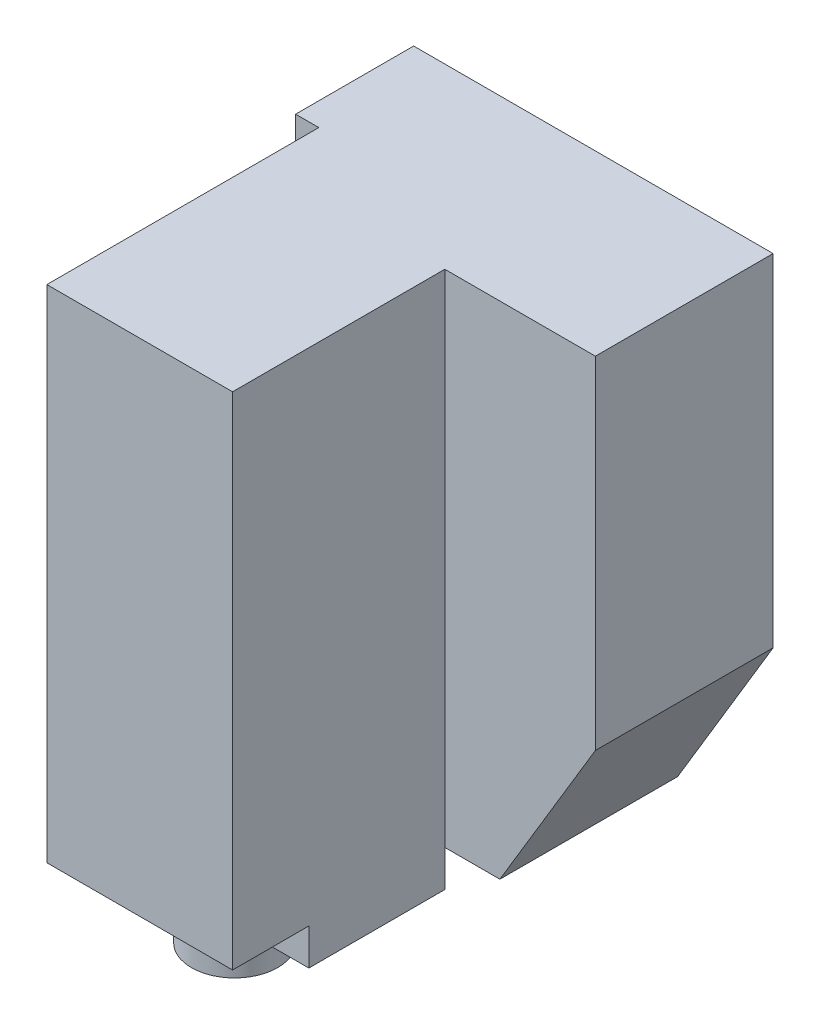
SolidWorks part; units mm, degrees
ref_plane "Front Plane" through (0, 0, 0) normal (0, 0, 1) x (1, 0, 0)
ref_plane "Top Plane" through (0, 0, 0) normal (0, 1, 0) x (1, 0, 0)
ref_plane "Right Plane" through (0, 0, 0) normal (1, 0, 0) x (0, 0, -1)
sketch "Sketch1" plane through (0, 0, 0) normal (0, 0, 1) x (1, 0, 0)
  line L0 (-280, 755) -> (-280, 0)
  line L1 (-280, 0) -> (0, 0)
  line L2 (0, 0) -> (0, 755)
  line L3 (-280, 755) -> (0, 755)
  dimension "D1" = 280
  dimension "D2" = 755
extrude "Boss-Extrude1" add sketch "Sketch1" along normal blind 588
sketch "Sketch4" plane through (0, 0, 0) normal (0, -1, 0) x (1, 0, 0)
  line L1 (-280, 588) -> (0, 588) construction
  line L5 (-280, 588) -> (-280, 0) construction
  circle A0 centre (-160, 425) radius 65
  circle A1 centre (-160, 425) radius 81
  circle A2 centre (-160, 425) radius 37
  dimension "D1" = 130
  dimension "D2" = 16
  dimension "D3" = 82
  dimension "D4" = 39
  dimension "D5" = 74
extrude "Boss-Extrude2" add sketch "Sketch4" along normal blind 20 contours A1
extrude "Boss-Extrude3" add sketch "Sketch4<3>" along normal blind 106 from surface contours A0 starting at face at (-160, -20, 344)
sketch "Sketch4<3>" plane through (0, 0, 0) normal (0, -1, 0) x (1, 0, 0) same geometry as "Sketch4"
extrude "Boss-Extrude4" add sketch "Sketch4<4>" along normal blind 13 from surface contours A2 region at (-160, 0, 425) starting at face at (-160, -126, 360)
sketch "Sketch4<4>" plane through (0, 0, 0) normal (0, -1, 0) x (1, 0, 0) same geometry as "Sketch4"
ref_plane "Plane1" through (0, 0, 268) normal (0, 0, 1) x (1, 0, 0)
sketch "Sketch5" plane through (0, 0, 268) normal (0, 0, -1) x (-1, 0, 0)
  line L0 (0, 0) -> (-83, 0)
  line L1 (-83, 0) -> (-227, 240.1333)
  line L2 (-227, 240.1333) -> (-227, 755)
  line L3 (-227, 755) -> (0, 755)
  line L4 (0, 755) -> (0, 0)
  line L5 (0, 755) -> (280, 755) construction
  dimension "D1" = 83
  dimension "D2" = 227
  dimension "D3" = 280
extrude "Boss-Extrude5" add sketch "Sketch5" along normal up to surface (268 mm away) contours L2 L3 L4 L0 L1 up to face at (-140, 377.5, 0)
ref_plane "Plane2" through (0, 0, 178) normal (0, 0, 1) x (1, 0, 0)
sketch "Sketch6" plane through (0, 0, 178) normal (0, 0, 1) x (1, 0, 0)
  line L0 (-315, -70) -> (-315, 755)
  line L1 (-315, 755) -> (-280, 755)
  line L2 (-280, 755) -> (-280, 0) construction
  line L3 (-280, 0) -> (0, 0) construction
  line L4 (-315, -70) -> (0, -70)
  line L5 (0, 0) -> (0, -70)
  line L6 (-280, 755) -> (-280, 0)
  line L7 (-280, 0) -> (0, 0)
  dimension "D1" = 35
  dimension "D2" = 70
extrude "Boss-Extrude6" add sketch "Sketch6" against normal up to surface (178 mm away) contours L7 L6 L1 L0 L4 L5 region at (-306.1691, 342.5, 178) up to face at (-4.6, 350.0267, 0)
sketch "Sketch7" plane through (0, 0, 0) normal (0, -1, 0) x (1, 0, 0)
  line L0 (-280, 588) -> (0, 588) construction
  line L1 (-55, 473) -> (0, 473)
  line L2 (-55, 473) -> (-55, 268)
  line L3 (-55, 268) -> (0, 268)
  line L4 (0, 473) -> (0, 268)
  line L5 (0, 588) -> (0, 268) construction
  line L6 (0, 268) -> (83, 268) construction
  dimension "D1" = 115
  dimension "D2" = 55
extrude "Boss-Extrude7" add sketch "Sketch7" along normal blind 55
sketch "Sketch8" plane through (0, -139, 0) normal (0, -1, 0) x (1, 0, 0)
  line L0 (-160, 425) -> (-62.2663, 425) construction
  line L1 (-160, 425) -> (-160, 569.1924) construction
  point P0 (-160, 425)
ref_plane "Plane3" through (-160, 0, 0) normal (-1, 0, 0) x (0, 0, 1)
